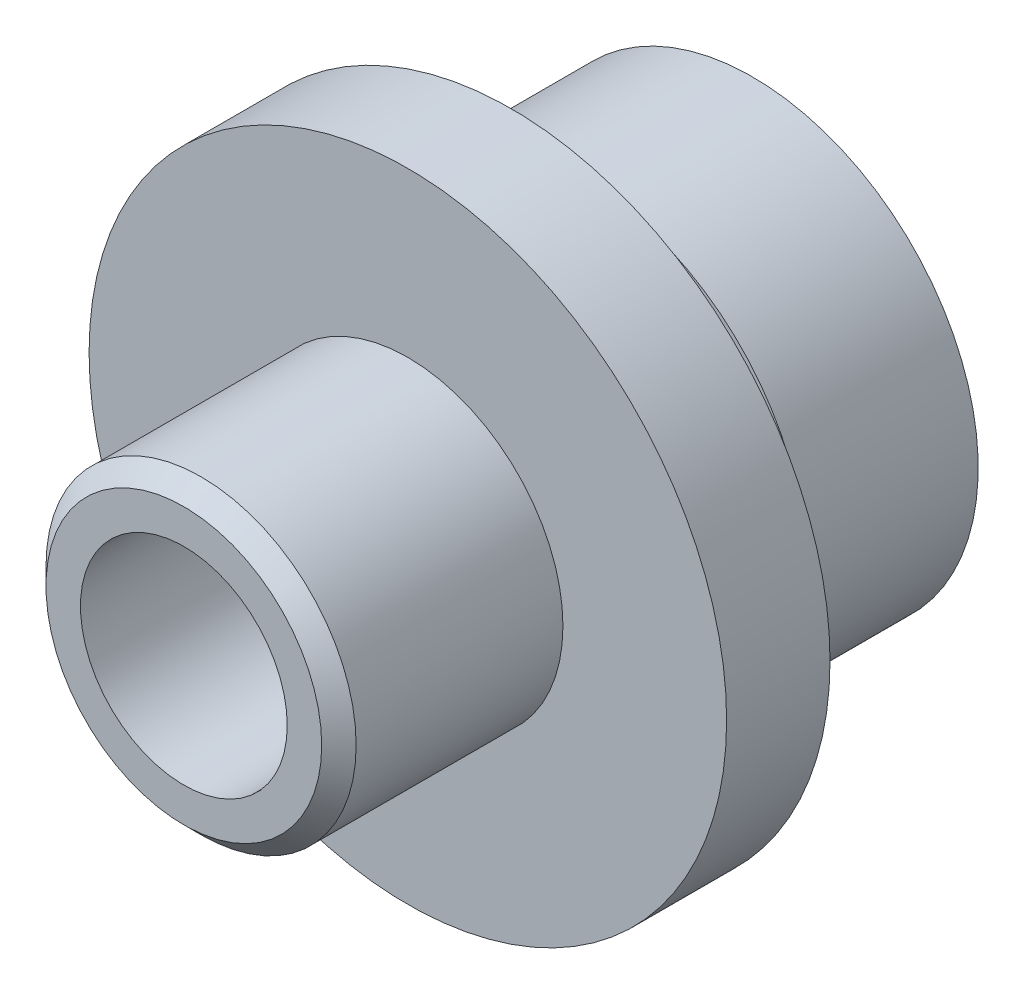
SolidWorks part; units mm, degrees
ref_plane "Front Plane" through (0, 0, 0) normal (0, 0, 1) x (1, 0, 0)
ref_plane "Top Plane" through (0, 0, 0) normal (0, 1, 0) x (1, 0, 0)
ref_plane "Right Plane" through (0, 0, 0) normal (1, 0, 0) x (0, 0, -1)
sketch "Sketch1" plane through (0, 0, 0) normal (0, 0, 1) x (1, 0, 0)
  circle A0 centre (0, 0) radius 3
  circle A1 centre (0, 0) radius 9.25
extrude "Boss-Extrude1" add sketch "Sketch1" along normal blind 16.5
sketch "Sketch2" plane through (0, 0, 16.5) normal (0, 0, 1) x (1, 0, 0)
  circle A0 centre (0, 0) radius 4.5
extrude "Cut-Extrude1" cut sketch "Sketch2" against normal blind 6.5 flip side to cut
sketch "Sketch3" plane through (0, 0, 0) normal (0, 0, -1) x (-1, 0, 0)
  circle A0 centre (0, 0) radius 6.55
extrude "Cut-Extrude2" cut sketch "Sketch3" against normal blind 7 flip side to cut
sketch "Sketch4" plane through (0, 0, 0) normal (0, 0, -1) x (-1, 0, 0)
  circle A0 centre (0, 0) radius 6
  circle A1 centre (0, 0) radius 7.5
extrude "Cut-Extrude3" cut sketch "Sketch4" against normal blind 3 from offset 5 offset against normal yes
chamfer "Chamfer1" distance 0.5 angle 45 1 edges at (4.5, 0, 16.5)
